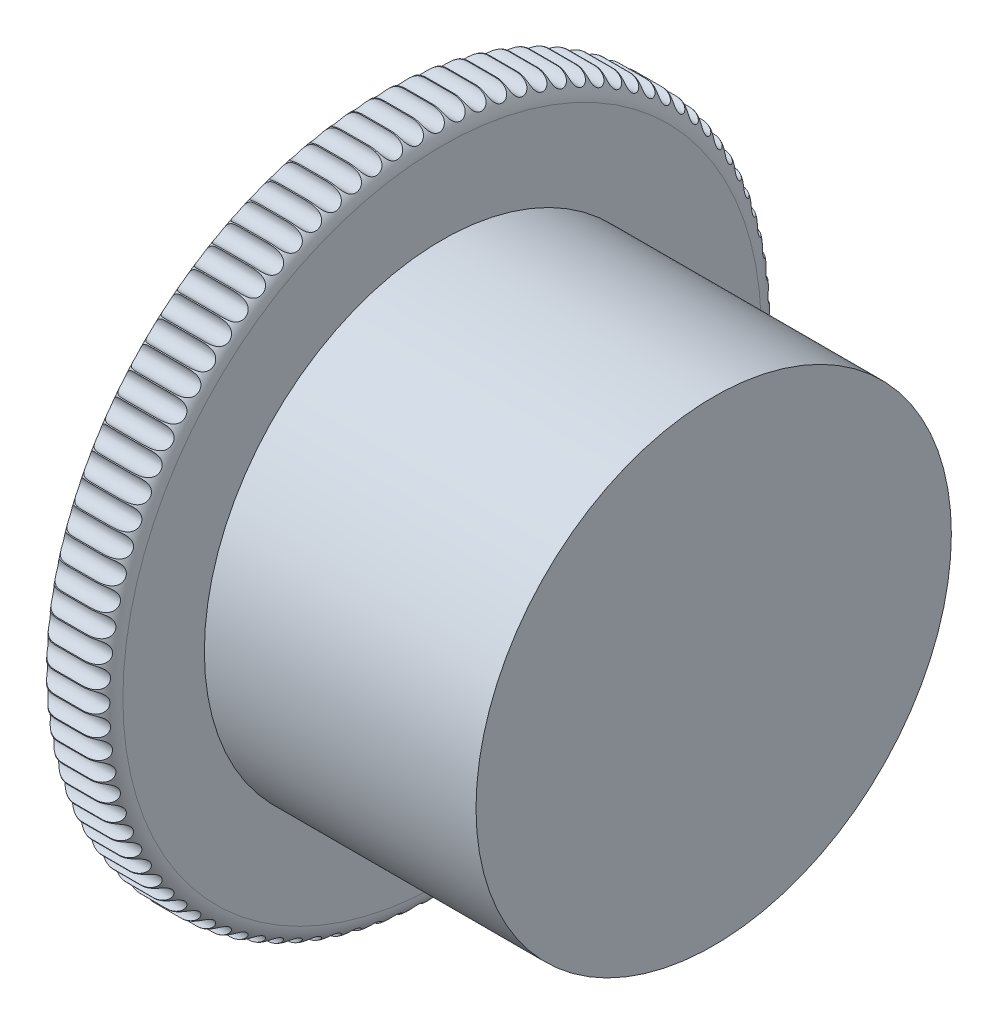
SolidWorks part; units mm, degrees
material "Латунь"
ref_plane "Спереди" through (0, 0, 0) normal (0, 0, 1) x (1, 0, 0)
ref_plane "Сверху" through (0, 0, 0) normal (0, 1, 0) x (1, 0, 0)
ref_plane "Справа" through (0, 0, 0) normal (1, 0, 0) x (0, 0, -1)
sketch "Эскиз1" plane through (0, 0, 0) normal (0, 0, 1) x (1, 0, 0)
  line L0 (0, 89.2947) -> (0, -56.2972) construction
  line L1 (-62.8463, 0) -> (137.1537, 0) construction
  line L2 (0, 0) -> (0, 47)
  line L3 (3, 50) -> (7, 50)
  line L4 (10, 47) -> (10, 35)
  line L5 (10, 35) -> (50, 35)
  line L6 (50, 35) -> (50, 0)
  line L7 (50, 0) -> (0, 0)
  arc A0 (0, 47) -> (3, 50) centre (3, 47) cw
  arc A1 (7, 50) -> (10, 47) centre (7, 47) cw
  point P13 (0, 50)
  dimension "D5" = 3
  dimension "D1" = 50
  dimension "D2" = 35
  dimension "D3" = 10
  dimension "D4" = 40
revolve "Повернуть1" add sketch "Эскиз1" angle 360 about L1
sketch "Эскиз2" plane through (0, 0, 0) normal (-1, 0, 0) x (0, 0, 1)
  line L0 (0, 53.924) -> (0, -54.1082) construction
  circle A0 centre (0, 50) radius 1.5
  circle A1 centre (0, 0) radius 50 construction
  dimension "D1" = 3
extrude "Вырез-Вытянуть1" cut sketch "Эскиз2" against normal up to surface (10 mm away) up to face at (10, 0, 47)
ref_axis "Ось1" through (50, 0, 0) along (-1, 0, 0)
pattern_circular "Круговой массив1" count 100 over 360 about axis through (50, 0, 0) along (-1, 0, 0) of "Вырез-Вытянуть1"
sketch "Эскиз3" plane through (0, 0, 0) normal (0, 0, 1) x (1, 0, 0)
  line L0 (-20.4929, 0) -> (66.0591, 0) construction
  line L1 (0, 53.5292) -> (0, -55.0995) construction
  line L2 (0, -35) -> (0, 35)
  line L3 (0, 47) -> (0, -47) construction
  arc A0 (0, 35) -> (0, -35) centre (-63.3488, 0) cw
  point P11 (0, 0)
  dimension "D1" = 35
extrude "Вырез-Вытянуть2" cut sketch "Эскиз3" against normal mid plane 10
